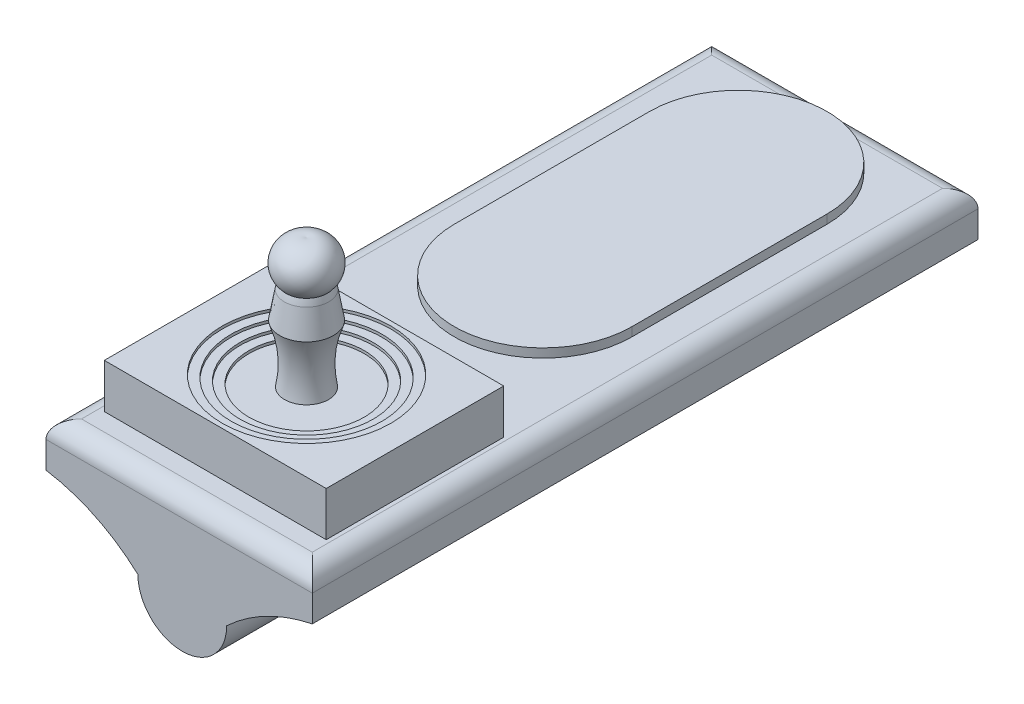
SolidWorks part; units mm, degrees
ref_plane "Front Plane" through (0, 0, 0) normal (0, 0, 1) x (1, 0, 0)
ref_plane "Top Plane" through (0, 0, 0) normal (0, 1, 0) x (1, 0, 0)
ref_plane "Right Plane" through (0, 0, 0) normal (1, 0, 0) x (0, 0, -1)
sketch "Sketch1" plane through (0, 0, 0) normal (0, 0, 1) x (1, 0, 0)
  line L1 (-15.3558, 10) -> (14.6442, 10)
  line L2 (-15.3558, 10) -> (-15.3558, 5)
  line L3 (14.6442, 10) -> (14.6442, 5)
  arc A1 (-5, 0) -> (5, 0) centre (0, 0) ccw
  arc A2 (-15.3558, 5) -> (-5, 0) centre (-18.5067, -14.7502) cw
  arc A3 (5, 0) -> (14.6442, 5) centre (18.6815, -14.5883) cw
  point P7 (-0.3558, 10)
  dimension "D1" = 30
  dimension "D2" = 5
  dimension "D4" = 10
  dimension "D7" = 10
  dimension "D5" = 20
  dimension "D6" = 20
  dimension "D3" = 5
extrude "Boss-Extrude2" add sketch "Sketch1" against normal blind 75
sketch "Sketch2" plane through (0, 0, -75) normal (0, 0, -1) x (-1, 0, 0)
  circle A0 centre (0, 0) radius 4
extrude "Cut-Extrude1" cut sketch "Sketch2" against normal blind 60
sketch "Sketch3" plane through (0, 10, 0) normal (0, 1, 0) x (1, 0, 0)
  line L2 (-10.3558, 41) -> (-10.3558, 63)
  line L4 (9.6442, 41) -> (9.6442, 63)
  line L5 (-7.715, 34.2293) -> (-0.1563, 46.5617) construction
  line L6 (-10.3019, 64.0372) -> (-0.1563, 46.5617) construction
  line L7 (-15.3558, 75) -> (-15.3558, 0) construction
  line L8 (14.6442, 75) -> (14.6442, 0) construction
  line L9 (14.6442, 75) -> (-15.3558, 75) construction
  line L10 (1.2249, 44.1826) -> (7.0034, 34.2293) construction
  arc A0 (9.6442, 63) -> (-10.3558, 63) centre (-0.3558, 63) ccw
  arc A1 (-10.3558, 41) -> (9.6442, 41) centre (-0.3558, 41) ccw
  point P0 (-0.1563, 46.5617)
  dimension "D1" = 12
  dimension "D2" = 5
  dimension "D3" = 5
  dimension "D4" = 22
extrude "Boss-Extrude3" add sketch "Sketch3" along normal blind 1
sketch "Sketch4" plane through (0, 10, 0) normal (0, 1, 0) x (1, 0, 0)
  line L0 (14.6442, 0) -> (-15.3558, 0) construction
  line L1 (-12.7866, 24) -> (12.2134, 24)
  line L2 (-12.7866, 24) -> (-12.7866, 4)
  line L3 (-12.7866, 4) -> (12.2134, 4)
  line L4 (12.2134, 24) -> (12.2134, 4)
  line L5 (-12.7866, 24) -> (12.2134, 4) construction
  line L6 (-12.7866, 4) -> (12.2134, 24) construction
  point P0 (-0.2866, 14)
  dimension "D1" = 25
  dimension "D2" = 20
  dimension "D3" = 4
extrude "Boss-Extrude4" add sketch "Sketch4" along normal blind 5
sketch "Sketch5" plane through (0, 15, 0) normal (0, 1, 0) x (1, 0, 0)
  circle A0 centre (0, 14) radius 9.5
extrude "Cut-Extrude5" cut sketch "Sketch5" against normal blind 0.3
sketch "Sketch9" plane through (0, 14.7, 0) normal (0, 1, 0) x (1, 0, 0)
  circle A0 centre (0, 14) radius 8.5
extrude "Cut-Extrude6" cut sketch "Sketch9" against normal blind 0.3
sketch "Sketch10" plane through (0, 14.4, 0) normal (0, 1, 0) x (1, 0, 0)
  circle A0 centre (0, 14) radius 7.5
extrude "Cut-Extrude7" cut sketch "Sketch10" against normal blind 0.3
sketch "Sketch11" plane through (0, 14.1, 0) normal (0, 1, 0) x (1, 0, 0)
  circle A0 centre (0, 14) radius 6.5
  dimension "D1" = 13
extrude "Cut-Extrude8" cut sketch "Sketch11" against normal blind 0.3
sketch "Sketch12" plane through (0, 0, 0) normal (1, 0, 0) x (0, 0, -1)
  line L0 (14, 15) -> (14, 13.6779)
  line L1 (4, 15) -> (24, 15) construction
  line L2 (14, 13.6779) -> (14, 26.6779) construction
  line L3 (14, 26.6779) -> (13, 26.6779)
  line L4 (11.4943, 23.3565) -> (10.9647, 20.3337)
  line L5 (14, 13.6779) -> (11.5, 13.6779)
  line L6 (14, 15) -> (14, 26.6779)
  arc A0 (11.4943, 23.3565) -> (13, 26.6779) centre (21.4008, 20.8677) cw
  arc A1 (10.9647, 20.3337) -> (11.5, 13.6779) centre (-0.2568, 16.0817) cw
  dimension "D2" = 12
  dimension "D1" = 13
revolve "Revolve2" add sketch "Sketch12" angle 360 about L2
sketch "Sketch13" plane through (0, 0, 0) normal (1, 0, 0) x (0, 0, -1)
  line L0 (14, 23.4035) -> (14, 28.4035) construction
  line L1 (14, 15) -> (14, 26.6779) construction
  line L2 (14, 23.4035) -> (14, 28.4035)
  arc A0 (14, 28.4035) -> (14, 23.4035) centre (14.5267, 25.9035) cw
revolve "Revolve3" add sketch "Sketch13" angle 360 about L0
fillet "Fillet1" radius 2 4 edges at (-0.3558, 10, -75) (14.6442, 10, -37.5) (-0.3558, 10, 0) (-15.3558, 10, -37.5)
